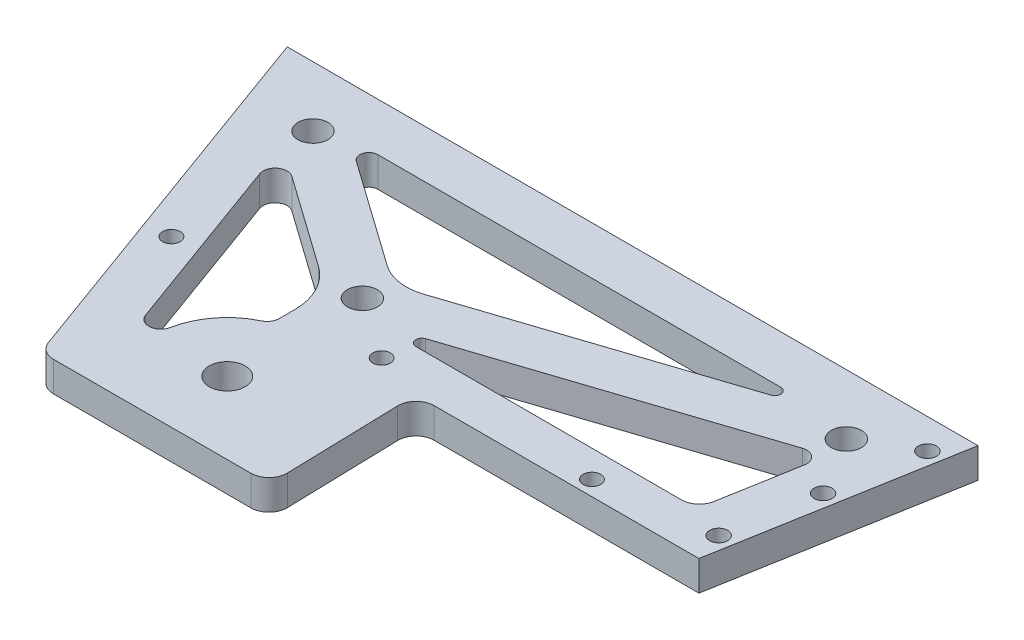
SolidWorks part; units mm, degrees
material "6061-T6 (SS)"
ref_plane "Front Plane" through (0, 0, 0) normal (1, 0, 0) x (0, 1, 0)
ref_plane "Top Plane" through (0, 0, 0) normal (0, 0, 1) x (0, 1, 0)
ref_plane "Right Plane" through (0, 0, 0) normal (0, 1, 0) x (-1, 0, 0)
sketch "Sketch1" plane through (0, 0, 0) normal (0, 1, 0) x (-1, 0, 0)
  line L0 (-72.4911, -52.5) -> (42.5089, -52.5)
  line L1 (42.5089, -52.5) -> (19.7513, 10.0261)
  line L2 (16.9322, 12) -> (-15.9516, 12)
  line L3 (-18.9505, 8.9198) -> (-18.4467, -9.9198)
  line L4 (-21.4457, -13) -> (-65.5261, -13)
  line L5 (-65.5261, -13) -> (-72.4911, -52.5)
  circle A0 centre (0, 0) radius 3
  circle A1 centre (0, 0) radius 22.5 construction
  circle A2 centre (0, 0) radius 40.4 construction
  circle A3 centre (-31.7358, -25) radius 27.5 construction
  circle A4 centre (-31.7358, -25) radius 8 construction
  circle A5 centre (-31.7358, -25) radius 9.5 construction
  circle A6 centre (-31.7358, -17) radius 1.5
  circle A7 centre (-31.7358, -33) radius 1.5
  circle A8 centre (-41.2358, -25) radius 1.5
  circle A9 centre (-22.2358, -25) radius 1.5
  arc A10 (-15.9516, 12) -> (-18.9505, 8.9198) centre (-15.9516, 9) ccw
  arc A11 (19.7513, 10.0261) -> (16.9322, 12) centre (16.9322, 9) ccw
  arc A12 (-18.4467, -9.9198) -> (-21.4457, -13) centre (-21.4457, -10) cw
  circle A13 centre (-31.7358, -25) radius 3
  point P25 (-19.0329, 12)
  point P28 (19.0329, 12)
  point P31 (-18.3644, -13)
  dimension "D1" = 6
  dimension "D2" = 45
  dimension "D3" = 80.8
  dimension "D4" = 55
  dimension "D11" = 16
  dimension "D12" = 19
  dimension "D13" = 3
  dimension "D14" = 3
  dimension "D15" = 3
  dimension "D16" = 3
  dimension "D17" = 6
  dimension "D5" = 25
  dimension "D6" = 115
  dimension "D7" = 12
  dimension "D8" = 13
  dimension "D9" = 80
  dimension "D10" = 70
extrude "Boss-Extrude2" add sketch "Sketch1" along normal blind 5 contours L4 L5 L0 L1 L2 L3 A9 A8 A7 A6 A0 | A8 | A9 | A7 | A13 | A6 region at (12.707, 0, -26.9714) region at (31.7358, 0, -33) region at (41.2358, 0, -25) region at (22.2358, 0, -25) region at (31.7358, 0, -25)
sketch "Sketch2" plane through (0, 5, 0) normal (0, 1, 0) x (-1, 0, 0)
  line L0 (42.5089, -52.5) -> (19.7513, 10.0261) construction
  line L1 (-72.4911, -52.5) -> (42.5089, -52.5) construction
  line L5 (-72.4911, -52.5) -> (42.5089, -52.5) construction
  line L6 (-65.5261, -13) -> (-72.4911, -52.5) construction
  circle A0 centre (28.2275, -42.5) radius 10 construction
  circle A1 centre (28.2275, -42.5) radius 2.5
  circle A2 centre (0, -22.5) radius 2.5
  circle A3 centre (-60.5735, -42.5) radius 10 construction
  circle A4 centre (-60.5735, -42.5) radius 2.5
  circle A5 centre (0, 0) radius 22.5 construction
  dimension "D1" = 20
  dimension "D2" = 5
  dimension "D4" = 5
  dimension "D5" = 20
  dimension "D6" = 5
extrude "Cut-Extrude1" cut sketch "Sketch2" against normal blind 5 contours A4 | A2 | A1
sketch "Sketch3" plane through (0, 5, 0) normal (0, 1, 0) x (-1, 0, 0)
  line L0 (-60.5481, -30.8381) -> (-59.5419, -25.1318)
  line L1 (-54.6178, -21) -> (-11.4564, -21)
  line L2 (16.9322, 12) -> (-15.9516, 12) construction
  line L3 (-49.0844, -44.5) -> (16.7383, -44.5)
  line L4 (12.9439, -20.641) -> (25.6898, -29.6719)
  line L5 (-72.4911, -52.5) -> (42.5089, -52.5) construction
  line L6 (-21.4457, -13) -> (-65.5261, -13) construction
  line L7 (-65.5261, -13) -> (-72.4911, -52.5) construction
  arc A0 (-51.582, -42.1087) -> (-58.6268, -33.7131) centre (-60.5735, -42.5) ccw
  arc A1 (-8.9659, -23.2826) -> (8.9989, -22.6416) centre (0, -22.5) ccw
  arc A2 (25.1104, -34.057) -> (19.236, -42.1087) centre (28.2275, -42.5) ccw
  circle A3 centre (0, 0) radius 12
  arc A4 (-54.6178, -21) -> (-59.5419, -25.1318) centre (-54.6178, -26) ccw
  arc A6 (-60.5481, -30.8381) -> (-58.6268, -33.7131) centre (-58.086, -31.2722) ccw
  arc A7 (-51.582, -42.1087) -> (-49.0844, -44.5) centre (-49.0844, -42) ccw
  arc A8 (16.7383, -44.5) -> (19.236, -42.1087) centre (16.7383, -42) ccw
  arc A9 (25.1104, -34.057) -> (25.6898, -29.6719) centre (24.2445, -31.7118) ccw
  arc A10 (-8.9659, -23.2826) -> (-11.4564, -21) centre (-11.4564, -23.5) ccw
  arc A11 (12.9439, -20.641) -> (8.9989, -22.6416) centre (11.4986, -22.6809) ccw
  dimension "D1" = 18
  dimension "D6" = 5
  dimension "D8" = 5
  dimension "D2" = 8
  dimension "D3" = 8
  dimension "D4" = 8
extrude "Cut-Extrude2" [suppressed] cut sketch "Sketch3" against normal blind 10 contours L4 A11 A1 A10 L1 A4 L0 A6 A0 A7 L3 A8 A2 A9
sketch "Sketch4" plane through (0, 5, 0) normal (0, 1, 0) x (-1, 0, 0)
  line L0 (-60.5735, -42.5) -> (0, -22.5) construction
  line L1 (0, -22.5) -> (0, 0) construction
  line L3 (28.2275, -42.5) -> (0, -22.5) construction
  line L4 (-47.9682, -42.5504) -> (-4.5007, -28.1984)
  line L5 (23.4647, -34.2232) -> (8.2188, -23.421)
  line L6 (4, -15.2615) -> (4, -12.6491)
  line L7 (-58.2243, -37.512) -> (-11.0909, -21.9496)
  line L8 (20.2868, -41.7761) -> (2.6325, -29.2675)
  line L10 (-47.6547, -44.5) -> (19.4196, -44.5)
  line L11 (-72.4911, -52.5) -> (42.5089, -52.5) construction
  line L12 (-61.8276, -38.7017) -> (-1.2541, -18.7017) construction
  line L14 (30.54, -39.2362) -> (2.3125, -19.2362) construction
  line L15 (4, -22.5) -> (4, 0) construction
  line L16 (-59.3194, -46.2983) -> (1.2541, -26.2983) construction
  line L17 (25.915, -45.7638) -> (-2.3125, -25.7638) construction
  line L18 (-58.5664, -22.4791) -> (-60.821, -35.2655)
  line L19 (-65.5261, -13) -> (-72.4911, -52.5) construction
  line L20 (-55.612, -20) -> (-11.4045, -20)
  line L21 (-21.4457, -13) -> (-65.5261, -13) construction
  line L22 (15.6181, -2.0083) -> (26.5004, -31.9073)
  line L24 (42.5089, -52.5) -> (19.7513, 10.0261) construction
  line L25 (16.9322, 12) -> (-15.9516, 12) construction
  arc A0 (5.1429, -10.8421) -> (11.776, -2.3077) centre (0, 0) ccw
  arc A1 (15.6181, -2.0083) -> (11.776, -2.3077) centre (13.7387, -2.6924) ccw
  arc A2 (23.4647, -34.2232) -> (26.5004, -31.9073) centre (24.621, -32.5913) ccw
  arc A3 (5.1429, -10.8421) -> (4, -12.6491) centre (6, -12.6491) ccw
  arc A4 (8.2188, -23.421) -> (4, -15.2615) centre (14, -15.2615) cw
  arc A5 (-11.0909, -21.9496) -> (-11.4045, -20) centre (-11.4045, -21) ccw
  arc A6 (2.6325, -29.2675) -> (-4.5007, -28.1984) centre (-1.9925, -35.7951) ccw
  arc A7 (-47.6547, -44.5) -> (-47.9682, -42.5504) centre (-47.6547, -43.5) cw
  arc A8 (20.2868, -41.7761) -> (19.4196, -44.5) centre (19.4196, -43) cw
  arc A9 (-55.612, -20) -> (-58.5664, -22.4791) centre (-55.612, -23) ccw
  arc A10 (-58.2243, -37.512) -> (-60.821, -35.2655) centre (-58.8514, -35.6128) cw
  dimension "D7" = 4
  dimension "D8" = 10
  dimension "D9" = 8
  dimension "D10" = 1
  dimension "D11" = 1.5
  dimension "D12" = 1
  dimension "D13" = 3
  dimension "D14" = 2
  dimension "D1" = 4
  dimension "D3" = 8
  dimension "D4" = 8.5
  dimension "D5" = 7
  dimension "D6" = 8
  dimension "D2" = 4
extrude "Cut-Extrude3" cut sketch "Sketch4" against normal blind 10
sketch "Sketch5" plane through (0, 0, 0) normal (0, -1, 0) x (1, 0, 0)
  line L0 (72.4911, -52.5) -> (-42.5089, -52.5) construction
  line L1 (-42.5089, -52.5) -> (-19.7513, 10.0261) construction
  line L2 (65.5261, -13) -> (72.4911, -52.5) construction
  line L3 (21.4457, -13) -> (65.5261, -13) construction
  circle A0 centre (69.0709, -47.5) radius 1.5
  circle A1 centre (66.4661, -32.7279) radius 1.5
  circle A2 centre (63.8614, -17.9558) radius 1.5
  circle A3 centre (45.2147, -15.5) radius 1.4664
  circle A4 centre (10.2147, -15.5) radius 1.4664
  circle A5 centre (-24.7853, -15.5) radius 1.4664
  dimension "D1" = 3
  dimension "D5" = 4
  dimension "D2" = 5
  dimension "D3" = 2.5
  dimension "D4" = 3
  dimension "D6" = 2.5
  dimension "D7" = 3
extrude "Cut-Extrude4" cut sketch "Sketch5" against normal up to surface (5 mm away) up to face at (-12.4025, 5, -16.6767)
